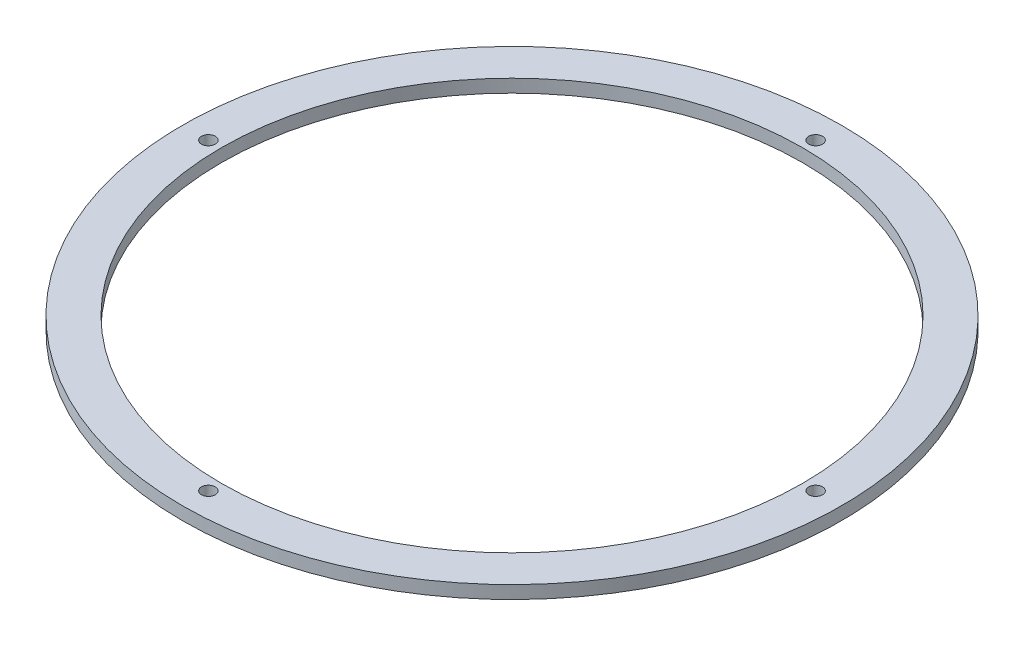
SolidWorks part; units mm, degrees
material "Pine"
ref_plane "Front Plane" through (0, 0, 0) normal (0, 0, 1) x (1, 0, 0)
ref_plane "Top Plane" through (0, 0, 0) normal (0, 1, 0) x (1, 0, 0)
ref_plane "Right Plane" through (0, 0, 0) normal (1, 0, 0) x (0, 0, -1)
sketch "Sketch1" plane through (0, 0, 0) normal (0, 1, 0) x (1, 0, 0)
  circle A0 centre (0, 0) radius 161.4
  circle A1 centre (0, 0) radius 136
  circle A3 centre (0, 0) radius 148.7 construction
  circle A4 centre (0, 0) radius 142.35
  dimension "D1" = 25.4
  dimension "D2" = 272
  dimension "D3" = 12.7
  dimension "D4" = 6.35
extrude "Boss-Extrude1" add sketch "Sketch1" along normal blind 6.35 contours A0 A4 region at (-156.8349, 0, 0)
sketch "Sketch2" plane through (0, 6.35, 0) normal (0, 1, 0) x (1, 0, 0)
  line L0 (0, 0) -> (0, -161.4) construction
  circle A1 centre (0, 0) radius 161.4 construction
  point P6 (0, -148.7)
  point P7 (0, -161.4)
  dimension "D1" = 12.7
hole_wizard "1/4 Clearance Hole1" positions "Sketch2" profile "Sketch3" hole size "1/4" standard "ANSI Inch" end condition through all
sketch "Sketch3" plane through (0, 6.35, 148.7) normal (1, 0, 0) x (0, 0, 1)
  line L0 (0, 0) -> (0, 6.35)
  line L1 (0, 6.35) -> (3.3782, 6.35)
  line L2 (3.3782, 6.35) -> (3.3782, 0)
  line L5 (3.3782, 0) -> (0, 0)
  line L11 (0, -6.35) -> (0, 107.95) construction
  dimension "Thru Hole Dia." = 6.7564
  dimension "Thru Hole Depth" = 6.35
pattern_circular "CirPattern1" count 4 every 90 about axis through (0, 6.35, 0) along (0, -1, 0) of "1/4 Clearance Hole1"
